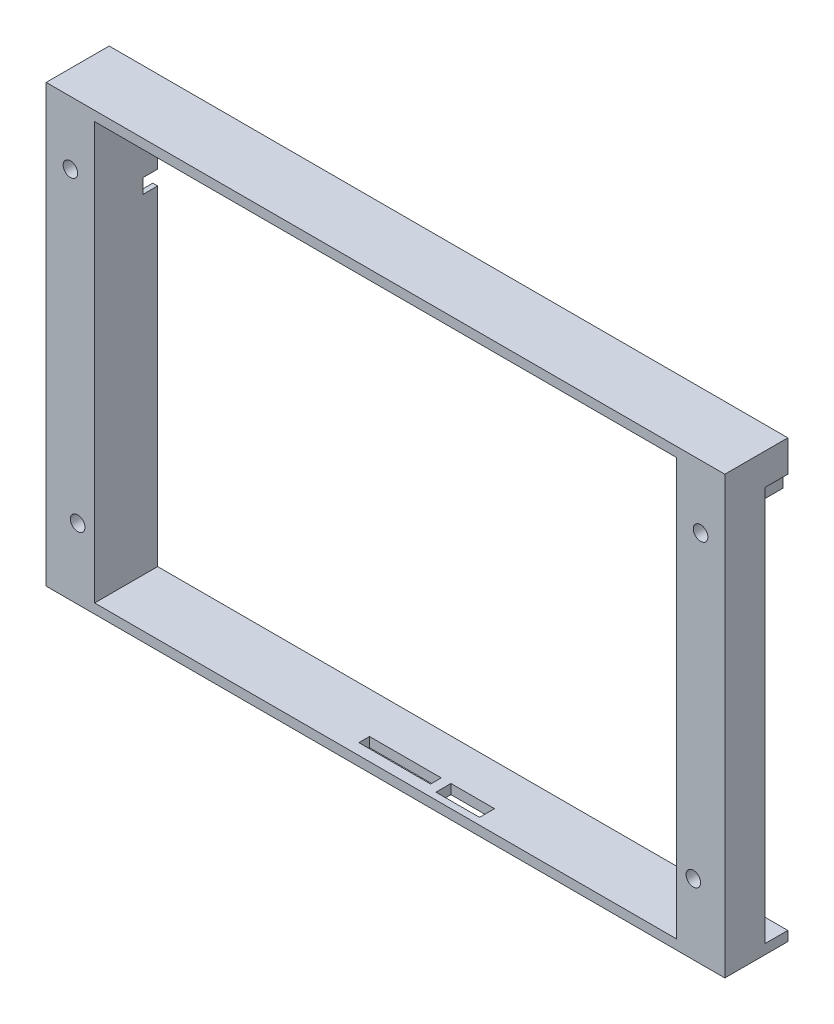
SolidWorks part; units mm, degrees
ref_plane "Front Plane" through (0, 0, 0) normal (0, 0, 1) x (1, 0, 0)
ref_plane "Top Plane" through (0, 0, 0) normal (0, 1, 0) x (1, 0, 0)
ref_plane "Right Plane" through (0, 0, 0) normal (1, 0, 0) x (0, 0, -1)
sketch "Sketch1" plane through (0, 0, 0) normal (0, 0, 1) x (1, 0, 0)
  line L8 (71.473, -52.326) -> (71.473, 37.674)
  line L9 (71.473, 37.674) -> (-68.527, 37.674)
  line L10 (-68.527, 37.674) -> (-68.527, -52.326)
  line L11 (-68.527, -52.326) -> (71.473, -52.326)
  line L12 (-58.527, -50.326) -> (61.473, -50.326)
  line L13 (61.473, 35.674) -> (61.473, -50.326)
  line L14 (-58.527, 35.674) -> (61.473, 35.674)
  line L15 (-58.527, 35.674) -> (-58.527, -50.326)
extrude "Boss-Extrude1" add sketch "Sketch1" along normal blind 13
sketch "Sketch13" plane through (0, 0, 0) normal (0, 0, -1) x (-1, 0, 0)
  line L0 (59.527, -50.326) -> (67.527, -50.326)
  line L1 (67.527, -50.326) -> (67.527, 27.674)
  line L2 (67.527, 27.674) -> (59.527, 27.674)
  line L3 (59.527, 27.674) -> (59.527, -50.326)
  line L4 (68.527, 37.674) -> (68.527, -52.326) construction
  line L5 (67.527, 30.674) -> (68.527, 30.674)
  line L6 (67.527, 30.674) -> (67.527, -50.326)
  line L7 (67.527, -50.326) -> (68.527, -50.326)
  line L8 (68.527, 30.674) -> (68.527, -50.326)
  line L10 (69.727, -45.326) -> (62.727, -45.326)
  line L11 (69.727, -45.326) -> (69.727, -41.326)
  line L12 (69.727, -41.326) -> (62.727, -41.326)
  line L13 (62.727, -45.326) -> (62.727, -41.326)
  circle A0 centre (62.027, -37.826) radius 1.5
  circle A1 centre (63.527, 24.674) radius 1.5
  line M2 (68.527, -52.326) -> (68.527, 37.674)
extrude "Cut-Extrude5" cut sketch "Sketch13" against normal blind 5.7 contours L10 L13 L12 L1 L2 L3 L0 A1 A0 | L13 L10 L6 L12 region at (-63.4929, -10.3995, 0) region at (-65.127, -43.326, 0)
extrude "Cut-Extrude6" cut sketch "Sketch13<6>" against normal blind 4.7 contours L12 L5 L6 L1 M2 | L10 L1 L7 M2 | L8 L12 L6 L10 region at (-68.027, -47.826, 0) region at (-68.027, -43.326, 0) region at (-68.027, -5.326, 0)
sketch "Sketch13<6>" plane through (0, 0, 0) normal (0, 0, -1) x (-1, 0, 0) same geometry as "Sketch13"
extrude "Cut-Extrude7" cut sketch "Sketch13<7>" against normal through all both and the other way through all contours A0 | A1 region at (-62.027, -37.826, 0) region at (-63.527, 24.674, 0)
sketch "Sketch13<7>" plane through (0, 0, 0) normal (0, 0, -1) x (-1, 0, 0) same geometry as "Sketch13"
ref_plane "Plane1" through (1.473, 0, 0) normal (1, 0, 0) x (0, 0, -1)
sketch "Sketch15" plane through (61.473, 0, 0) normal (-1, 0, 0) x (0, 0, 1)
  line L0 (0, -50.326) -> (0, 35.674) construction
  line L1 (0, 20.674) -> (3, 20.674)
  line L2 (0, 20.674) -> (0, 17.674)
  line L3 (0, 17.674) -> (3, 17.674)
  line L4 (3, 20.674) -> (3, 17.674)
  line L5 (13, 35.674) -> (0, 35.674) construction
  dimension "D1" = 15
  dimension "D2" = 3
  dimension "D3" = 3
extrude "Cut-Extrude8" cut sketch "Sketch15" against normal blind 10
mirror "Mirror1" about plane through (1.473, 0, 0) normal (1, 0, 0) of "Cut-Extrude8", "Cut-Extrude5", "Cut-Extrude7", "Cut-Extrude6"
sketch "Sketch16" plane through (0, 27.674, 0) normal (0, -1, 0) x (1, 0, 0)
  line L1 (-59.527, 5.7) -> (-67.527, 5.7)
  line L2 (-59.527, 5.7) -> (-59.527, 0)
  line L3 (-59.527, 0) -> (-67.527, 0)
  line L4 (-67.527, 5.7) -> (-67.527, 0)
  line L5 (-67.527, 4.7) -> (-68.527, 4.7)
  line L6 (-67.527, 4.7) -> (-67.527, 0)
  line L7 (-67.527, 0) -> (-68.527, 0)
  line L8 (-68.527, 4.7) -> (-68.527, 0)
  line L9 (62.473, 5.7) -> (70.473, 5.7)
  line L10 (62.473, 5.7) -> (62.473, 0)
  line L11 (62.473, 0) -> (70.473, 0)
  line L12 (70.473, 5.7) -> (70.473, 0)
  line L13 (70.473, 4.7) -> (71.473, 4.7)
  line L14 (70.473, 4.7) -> (70.473, 0)
  line L15 (70.473, 0) -> (71.473, 0)
  line L16 (71.473, 4.7) -> (71.473, 0)
  line M1 (-67.527, 0) -> (-59.527, 0)
  line M2 (-59.527, 0) -> (-59.527, 5.7)
  line M3 (-59.527, 5.7) -> (-67.527, 5.7)
  line M4 (-67.527, 5.7) -> (-67.527, 4.7)
  line M5 (-67.527, 4.7) -> (-67.527, 0)
extrude "Cut-Extrude9" cut sketch "Sketch16" against normal blind 0.5 contours M5 M1 M2 M3 M4 | L12 L9 L10 L11 region at (-63.527, 27.674, 2.85) region at (66.473, 27.674, 2.85)
extrude "Cut-Extrude10" cut sketch "Sketch16<3>" against normal blind 3.5 contours L5 L8 L7 M5 | L16 L13 L12 L15 region at (-68.027, 27.674, 2.35) region at (70.973, 27.674, 2.35)
sketch "Sketch16<3>" plane through (0, 27.674, 0) normal (0, -1, 0) x (1, 0, 0) same geometry as "Sketch16"
sketch "Sketch17" plane through (0, -50.326, 0) normal (0, 1, 0) x (1, 0, 0)
  line L0 (-59.527, -5.7) -> (-67.527, -5.7) construction
  line L1 (-65.027, -3.7) -> (-63.027, -3.7)
  line L2 (-65.027, -3.7) -> (-65.027, -5.7)
  line L3 (-65.027, -5.7) -> (-63.027, -5.7)
  line L4 (-63.027, -3.7) -> (-63.027, -5.7)
  line L5 (-65.027, -3.7) -> (-63.027, -5.7) construction
  line L6 (-65.027, -5.7) -> (-63.027, -3.7) construction
  line L7 (-67.527, -5.7) -> (-67.527, -4.7) construction
  line L8 (62.473, -5.7) -> (70.473, -5.7) construction
  line L9 (65.973, -3.7) -> (67.973, -3.7)
  line L10 (65.973, -3.7) -> (65.973, -5.7)
  line L11 (65.973, -5.7) -> (67.973, -5.7)
  line L12 (67.973, -3.7) -> (67.973, -5.7)
  line L13 (65.973, -3.7) -> (67.973, -5.7) construction
  line L14 (65.973, -5.7) -> (67.973, -3.7) construction
  line L15 (70.473, -5.7) -> (70.473, -4.7) construction
  point P0 (-64.027, -4.7)
  point P9 (66.973, -4.7)
  dimension "D1" = 3.5
  dimension "D2" = 2
  dimension "D3" = 2
  dimension "D4" = 3.5
  dimension "D5" = 2
  dimension "D6" = 2
extrude "Cut-Extrude11" cut sketch "Sketch17" against normal blind 1
sketch "Sketch18" plane through (0, -52.326, 0) normal (0, 1, 0) x (1, 0, 0)
  line L1 (-6.327, -10.7) -> (8.473, -10.7)
  line L2 (-6.327, -10.7) -> (-6.327, -8.5)
  line L3 (-6.327, -8.5) -> (8.473, -8.5)
  line L4 (8.473, -10.7) -> (8.473, -8.5)
  line L5 (10.473, -11.6) -> (19.473, -11.6)
  line L6 (10.473, -11.6) -> (10.473, -8.5)
  line L7 (10.473, -8.5) -> (19.473, -8.5)
  line L8 (19.473, -11.6) -> (19.473, -8.5)
extrude "Cut-Extrude13" cut sketch "Sketch18" along normal up to surface (2 mm away) up to face at (1.473, -50.326, 6.5)
